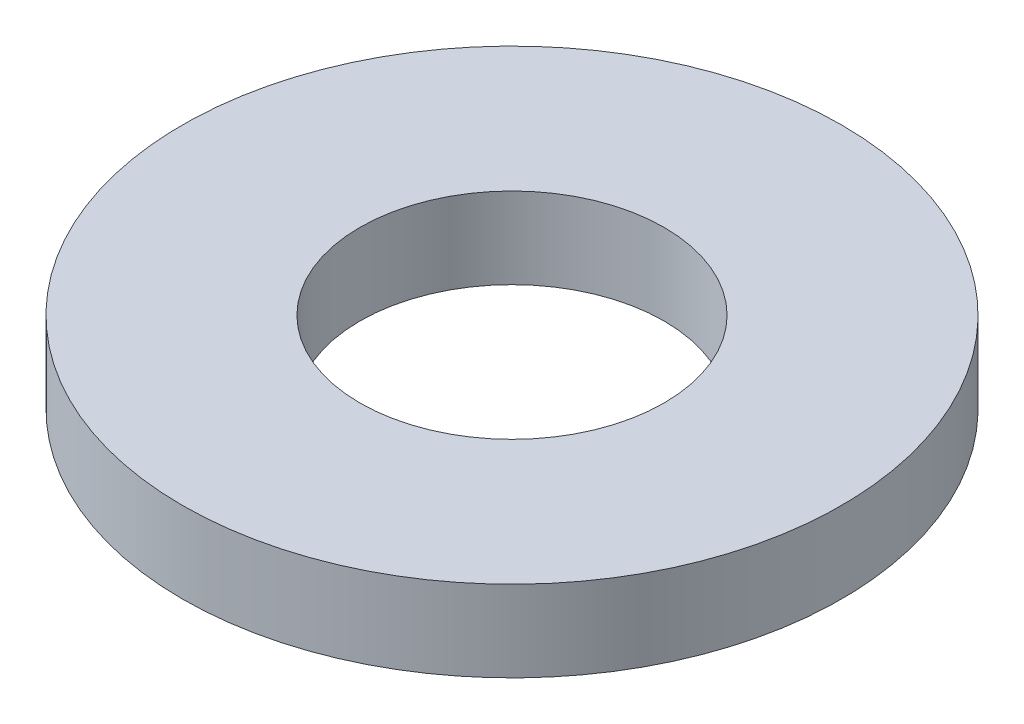
SolidWorks part; units mm, degrees
ref_plane "Front Plane" through (0, 0, 0) normal (0, 0, 1) x (1, 0, 0)
ref_plane "Top Plane" through (0, 0, 0) normal (0, 1, 0) x (1, 0, 0)
ref_plane "Right Plane" through (0, 0, 0) normal (1, 0, 0) x (0, 0, -1)
sketch "Sketch1" plane through (0, 0, 0) normal (0, 1, 0) x (1, 0, 0)
  circle A0 centre (0, 0) radius 65
  dimension "FLANGE_OD" = 130
extrude "Boss-Extrude1" add sketch "Sketch1" along normal blind 16
sketch "Sketch2" plane through (0, 0, 0) normal (0, 1, 0) x (1, 0, 0)
  circle A0 centre (0, 0) radius 30
  dimension "BORE_D" = 60
extrude "Cut-Extrude1" cut sketch "Sketch2" along normal through all
sketch "Sketch3" plane through (0, 16, 0) normal (0, 1, 0) x (1, 0, 0)
  circle A0 centre (0, 0) radius 22.9206 construction
  circle A1 centre (-22.9206, 0) radius 5.8866
  dimension "BOLT_D" = 11.7731
  dimension "BOLT_PCD" = 45.8411
extrude "Cut-Extrude2" cut sketch "Sketch3" against normal blind 15.2113 rebuild error yes
pattern_circular "CirPattern1" count 6 over 360 rebuild error yes
